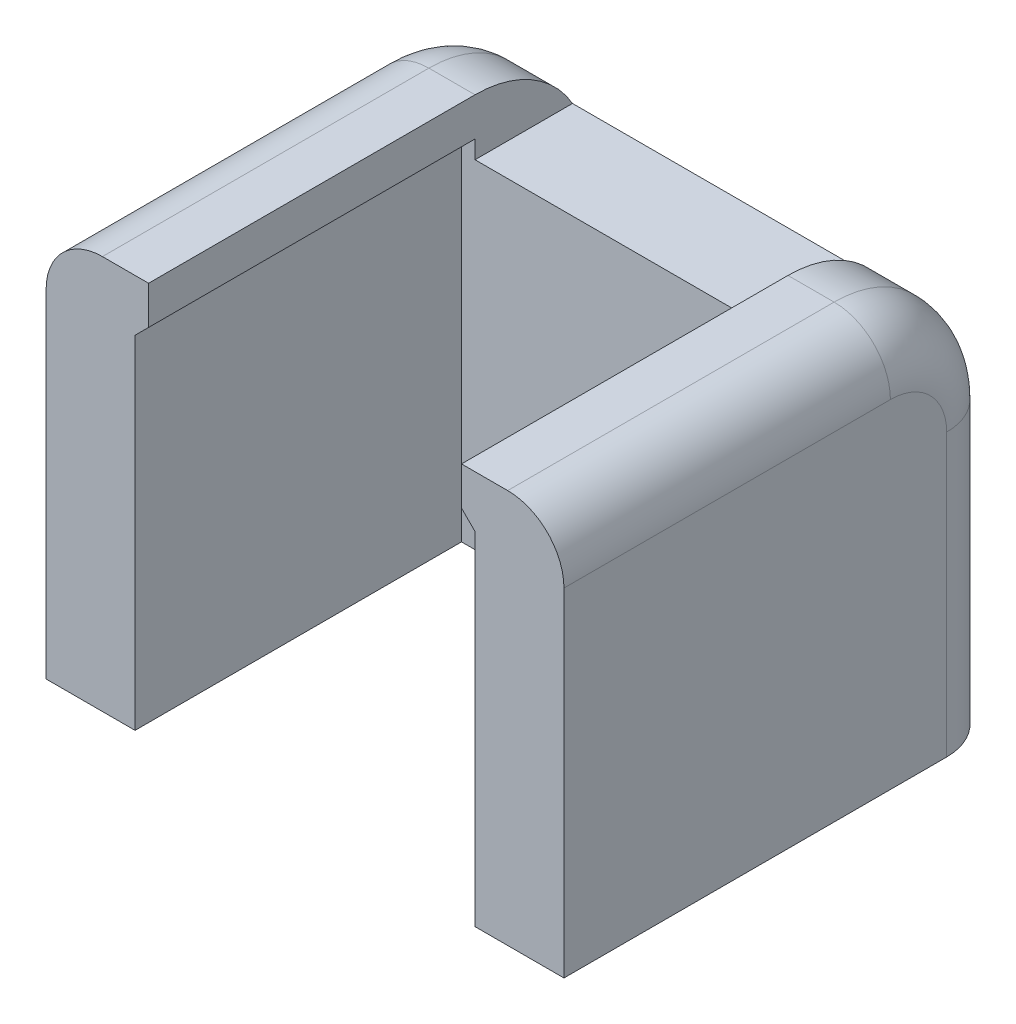
SolidWorks part; units mm, degrees
ref_plane "前视基准面" through (0, 0, 0) normal (0, 0, 1) x (1, 0, 0)
ref_plane "上视基准面" through (0, 0, 0) normal (0, 1, 0) x (1, 0, 0)
ref_plane "右视基准面" through (0, 0, 0) normal (1, 0, 0) x (0, 0, -1)
sketch "草图1" plane through (0, 0, 0) normal (0, 0, 1) x (1, 0, 0)
  line L1 (23, -17.5) -> (-23, -17.5)
  line L2 (23, -17.5) -> (23, 17.5)
  line L3 (23, 17.5) -> (-23, 17.5)
  line L4 (-23, -17.5) -> (-23, 17.5)
  line L5 (0, 17.5) -> (0, -17.5) construction
  line L6 (23, 0) -> (-23, 0) construction
  point P0 (0, 0)
  dimension "D1" = 46
  dimension "D2" = 35
extrude "凸台-拉伸1" add sketch "草图1" along normal blind 39
sketch "草图2" plane through (0, 0, 39) normal (0, 0, 1) x (1, 0, 0)
  line L0 (-23, -17.5) -> (23, -17.5) construction
  line L1 (-15.1, 12.5) -> (15.1, 12.5)
  line L2 (-15.1, 12.5) -> (-15.1, -17.5)
  line L3 (-15.1, -17.5) -> (15.1, -17.5)
  line L4 (15.1, 12.5) -> (15.1, -17.5)
  line L5 (0, -17.5) -> (0, 12.5) construction
  line L6 (-15.1, -2.5) -> (15.1, -2.5) construction
  point P0 (0, -2.5)
  dimension "D1" = 30.2
  dimension "D2" = 30
extrude "切除-拉伸1" cut sketch "草图2" against normal offset from surface (29 mm away) 10 up to face at (0, 0, 0)
sketch "草图4" plane through (0, 0, 39) normal (0, 0, 1) x (1, 0, 0)
  line L0 (23, 17.5) -> (-23, 17.5) construction
  line L1 (-13.9, 22.5) -> (13.9, 22.5)
  line L2 (-13.9, 22.5) -> (-13.9, 12.5)
  line L3 (-13.9, 12.5) -> (13.9, 12.5)
  line L4 (13.9, 22.5) -> (13.9, 12.5)
  line L5 (0, 12.5) -> (0, 22.5) construction
  line L6 (-13.9, 17.5) -> (13.9, 17.5) construction
  line L7 (15.1, 12.5) -> (-15.1, 12.5) construction
  line L8 (15.1, -17.5) -> (15.1, 12.5) construction
  point P0 (0, 17.5)
  dimension "D1" = 1.2
extrude "切除-拉伸2" cut sketch "草图4" against normal through all
hole_wizard "M6 凹头盖螺钉的柱形沉头孔2" positions "草图5" profile "草图6" counterbore size "M6" standard "ANSI Metric" end condition through all
sketch "草图5" plane through (0, 0, 0) normal (0, 0, -1) x (-1, 0, 0)
  line L0 (0, -2.5) -> (0, -17.5)
  line L1 (23, -17.5) -> (-23, -17.5) construction
  point P0 (0, -2.5)
  dimension "D1" = 15
sketch "草图6" plane through (0, -2.5, 0) normal (1, 0, 0) x (0, 1, 0)
  line L0 (0, 0) -> (0, 39)
  line L1 (0, 39) -> (3.25, 39)
  line L3 (3.25, 39) -> (3.25, 5)
  line L4 (3.25, 5) -> (5.5, 5)
  line L5 (5.5, 5) -> (5.5, 0)
  line L7 (5.5, 0) -> (0, 0)
  line L11 (0, -6.35) -> (0, 107.95) construction
  dimension "通孔孔直径" = 6.5
  dimension "通孔孔深度" = 39
  dimension "柱形沉头孔直径" = 11
  dimension "柱形沉头孔深度" = 5
chamfer "倒角1" distance 1.6 angle 45 2 edges at (13.9, 12.5, 24.5) (-13.9, 12.5, 24.5)
fillet "圆角3" radius 10 1 edges at (18.45, 17.5, 0)
fillet "圆角4" radius 5 6 edges at (-23, -5, 0) (-23, 14.5711, 2.9289) (23, -5, 0) (23, 14.5711, 2.9289) (-23, 17.5, 24.5) (23, 17.5, 24.5)
